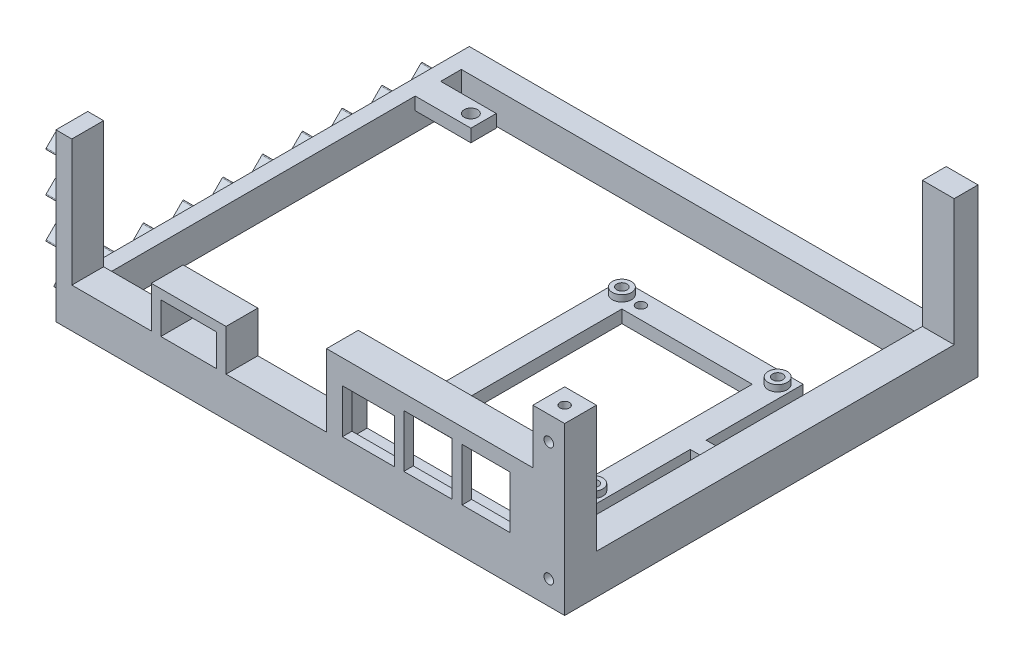
SolidWorks part; units mm, degrees
note: The reader was unsure of these and kept them because the rebuilt part matched: shared geometry of "Sketch14<3>".
ref_plane "Front Plane" through (0, 0, 0) normal (0, 0, 1) x (1, 0, 0)
ref_plane "Top Plane" through (0, 0, 0) normal (0, 1, 0) x (1, 0, 0)
ref_plane "Right Plane" through (0, 0, 0) normal (1, 0, 0) x (0, 0, -1)
sketch "Sketch1" plane through (0, 0, 0) normal (0, 1, 0) x (1, 0, 0)
  line L0 (0, -65) -> (0, 65) construction
  line L1 (-75, -65) -> (85, -65)
  line L2 (-75, -65) -> (-75, 65)
  line L3 (-75, 65) -> (85, 65)
  line L4 (85, -65) -> (85, 65)
  point P0 (0, 0)
  point P9 (0, 0)
  dimension "D1" = 75
  dimension "D2" = 85
extrude "Boss-Extrude1" add sketch "Sketch1" along normal blind 10
sketch "Sketch3" plane through (0, 10, 0) normal (0, 1, 0) x (1, 0, 0)
  line L6 (85, 65) -> (-75, 65) construction
  line L9 (-75, 65) -> (-75, -65) construction
  line L10 (75, 65) -> (75, -55)
  line L13 (75, -55) -> (-75, -55)
  line L14 (-75, -55) -> (-75, -65)
  line L15 (-75, -65) -> (85, -65)
  line L16 (85, -65) -> (85, 65)
  line L17 (85, 65) -> (75, 65)
  dimension "D1" = 10
extrude "Boss-Extrude2" add sketch "Sketch3" along normal blind 42.3
sketch "Sketch8" plane through (0, 0, -65) normal (0, 0, -1) x (-1, 0, 0)
  line L0 (-75, 10) -> (-85, 10) construction
  line L56 (-85, 52.3) -> (-85, 0) construction
  line L57 (-75, 10) -> (-75, 0) construction
  line L59 (-85, 0) -> (75, 0) construction
  line L60 (-80, 10) -> (-80, 52.3) construction
  line L126 (-85, 52.3) -> (-75, 52.3) construction
  line L139 (-75, 5) -> (75, 5) construction
  line L140 (75, 10) -> (75, 0) construction
  line L141 (-83.425, 31.15) -> (-76.575, 31.15) construction
  line L142 (-83.425, 31.15) -> (-80, 34.575)
  line L143 (-80, 34.575) -> (-76.575, 31.15)
  line L144 (-76.575, 31.15) -> (-80, 27.725)
  line L145 (-80, 27.725) -> (-83.425, 31.15)
  line L146 (-80, 40.225) -> (-83.425, 43.65)
  line L147 (-83.425, 43.65) -> (-80, 47.075)
  line L148 (-80, 47.075) -> (-76.575, 43.65)
  line L149 (-76.575, 43.65) -> (-80, 40.225)
  line L150 (-80, 15.225) -> (-83.425, 18.65)
  line L151 (-83.425, 18.65) -> (-80, 22.075)
  line L152 (-80, 22.075) -> (-76.575, 18.65)
  line L153 (-76.575, 18.65) -> (-80, 15.225)
  line L154 (0, 1.575) -> (0, 8.425) construction
  line L155 (0, 8.425) -> (-3.425, 5)
  line L156 (-3.425, 5) -> (0, 1.575)
  line L157 (0, 1.575) -> (3.425, 5)
  line L158 (3.425, 5) -> (0, 8.425)
  line L159 (15.925, 5) -> (12.5, 8.425)
  line L160 (12.5, 8.425) -> (9.075, 5)
  line L161 (9.075, 5) -> (12.5, 1.575)
  line L162 (12.5, 1.575) -> (15.925, 5)
  line L163 (28.425, 5) -> (25, 8.425)
  line L164 (25, 8.425) -> (21.575, 5)
  line L165 (21.575, 5) -> (25, 1.575)
  line L166 (25, 1.575) -> (28.425, 5)
  line L167 (40.925, 5) -> (37.5, 8.425)
  line L168 (37.5, 8.425) -> (34.075, 5)
  line L169 (34.075, 5) -> (37.5, 1.575)
  line L170 (37.5, 1.575) -> (40.925, 5)
  line L171 (53.425, 5) -> (50, 8.425)
  line L172 (50, 8.425) -> (46.575, 5)
  line L173 (46.575, 5) -> (50, 1.575)
  line L174 (50, 1.575) -> (53.425, 5)
  line L175 (65.925, 5) -> (62.5, 8.425)
  line L176 (62.5, 8.425) -> (59.075, 5)
  line L177 (59.075, 5) -> (62.5, 1.575)
  line L178 (62.5, 1.575) -> (65.925, 5)
  line L179 (-9.075, 5) -> (-12.5, 8.425)
  line L180 (-12.5, 8.425) -> (-15.925, 5)
  line L181 (-15.925, 5) -> (-12.5, 1.575)
  line L182 (-12.5, 1.575) -> (-9.075, 5)
  line L183 (-21.575, 5) -> (-25, 8.425)
  line L184 (-25, 8.425) -> (-28.425, 5)
  line L185 (-28.425, 5) -> (-25, 1.575)
  line L186 (-25, 1.575) -> (-21.575, 5)
  line L187 (-34.075, 5) -> (-37.5, 8.425)
  line L188 (-37.5, 8.425) -> (-40.925, 5)
  line L189 (-40.925, 5) -> (-37.5, 1.575)
  line L190 (-37.5, 1.575) -> (-34.075, 5)
  line L191 (-46.575, 5) -> (-50, 8.425)
  line L192 (-50, 8.425) -> (-53.425, 5)
  line L193 (-53.425, 5) -> (-50, 1.575)
  line L194 (-50, 1.575) -> (-46.575, 5)
  line L195 (-59.075, 5) -> (-62.5, 8.425)
  line L196 (-62.5, 8.425) -> (-65.925, 5)
  line L197 (-65.925, 5) -> (-62.5, 1.575)
  line L198 (-62.5, 1.575) -> (-59.075, 5)
  line L199 (-71.575, 5) -> (-75, 8.425)
  line L200 (-75, 8.425) -> (-78.425, 5)
  line L201 (-78.425, 5) -> (-75, 1.575)
  line L202 (-75, 1.575) -> (-71.575, 5)
  point P18 (-80, 31.15)
  point P31 (0, 5)
  dimension "D1" = 2
  dimension "D2" = 2
extrude "Cut-Extrude3" cut sketch "Sketch8" against normal blind 5.25
sketch "Sketch9" plane through (0, 10, 0) normal (0, 1, 0) x (1, 0, 0)
  line L1 (-75, 65) -> (-75, -55) construction
  line L5 (-70, -55) -> (75, -55)
  line L6 (-70, 51) -> (-70, 57.5)
  line L7 (-70, 43) -> (-70, -55)
  line L8 (75, -55) -> (75, 57.5)
  line L9 (75, 65) -> (75, -55) construction
  line L10 (75, 57.5) -> (-70, 57.5)
  line L12 (75, 65) -> (-75, 65) construction
  line L13 (-52.5, 47) -> (-56.5, 47) construction
  line L14 (-70, 43) -> (-52.5, 43)
  line L15 (-52.5, 43) -> (-52.5, 51)
  line L16 (-52.5, 51) -> (-70, 51)
  circle A1 centre (-56.5, 47) radius 2.1
  dimension "D2" = 4.2
  dimension "D4" = 5
  dimension "D1" = 7.5
  dimension "D5" = 17.5
extrude "Cut-Extrude4" cut sketch "Sketch9" against normal through all
sketch "Sketch10" plane through (-75, 0, 0) normal (-1, 0, 0) x (0, 0, 1)
  line L0 (55, 10) -> (65, 10) construction
  line L1 (10.5379, 5.2121) -> (7.7121, 8.0379)
  line L2 (7.2879, 8.0379) -> (4.4621, 5.2121)
  line L40 (65, 52.3) -> (65, 0) construction
  line L41 (55, 10) -> (55, 0) construction
  line L42 (-65, 0) -> (65, 0) construction
  line L43 (4.4621, 4.7879) -> (7.2879, 1.9621)
  line L57 (60, 10) -> (60, 52.3) construction
  line L94 (55, 52.3) -> (65, 52.3) construction
  line L111 (63.25, 31.15) -> (56.75, 31.15) construction
  line L112 (56.9621, 31.3621) -> (59.7879, 34.1879)
  line L113 (60.2121, 34.1879) -> (63.0379, 31.3621)
  line L114 (63.0379, 30.9379) -> (60.2121, 28.1121)
  line L115 (59.7879, 28.1121) -> (56.9621, 30.9379)
  line L124 (55, 5) -> (-65, 5) construction
  line L125 (-65, 10) -> (-65, 0) construction
  line L126 (-5, 8.25) -> (-5, 1.75) construction
  line L127 (-5.2121, 8.0379) -> (-8.0379, 5.2121)
  line L128 (-8.0379, 4.7879) -> (-5.2121, 1.9621)
  line L129 (-4.7879, 1.9621) -> (-1.9621, 4.7879)
  line L130 (-1.9621, 5.2121) -> (-4.7879, 8.0379)
  line L131 (59.7879, 40.6121) -> (56.9621, 43.4379)
  line L132 (56.9621, 43.8621) -> (59.7879, 46.6879)
  line L133 (60.2121, 46.6879) -> (63.0379, 43.8621)
  line L134 (63.0379, 43.4379) -> (60.2121, 40.6121)
  line L135 (59.7879, 15.6121) -> (56.9621, 18.4379)
  line L136 (56.9621, 18.8621) -> (59.7879, 21.6879)
  line L137 (60.2121, 21.6879) -> (63.0379, 18.8621)
  line L138 (63.0379, 18.4379) -> (60.2121, 15.6121)
  line L139 (7.7121, 1.9621) -> (10.5379, 4.7879)
  line L140 (23.0379, 5.2121) -> (20.2121, 8.0379)
  line L141 (19.7879, 8.0379) -> (16.9621, 5.2121)
  line L142 (16.9621, 4.7879) -> (19.7879, 1.9621)
  line L143 (20.2121, 1.9621) -> (23.0379, 4.7879)
  line L144 (35.5379, 5.2121) -> (32.7121, 8.0379)
  line L145 (32.2879, 8.0379) -> (29.4621, 5.2121)
  line L146 (29.4621, 4.7879) -> (32.2879, 1.9621)
  line L147 (32.7121, 1.9621) -> (35.5379, 4.7879)
  line L148 (48.0379, 5.2121) -> (45.2121, 8.0379)
  line L149 (44.7879, 8.0379) -> (41.9621, 5.2121)
  line L150 (41.9621, 4.7879) -> (44.7879, 1.9621)
  line L151 (45.2121, 1.9621) -> (48.0379, 4.7879)
  line L152 (60.5379, 5.2121) -> (57.7121, 8.0379)
  line L153 (57.2879, 8.0379) -> (54.4621, 5.2121)
  line L154 (54.4621, 4.7879) -> (57.2879, 1.9621)
  line L155 (57.7121, 1.9621) -> (60.5379, 4.7879)
  line L156 (-14.4621, 5.2121) -> (-17.2879, 8.0379)
  line L157 (-17.7121, 8.0379) -> (-20.5379, 5.2121)
  line L158 (-20.5379, 4.7879) -> (-17.7121, 1.9621)
  line L159 (-17.2879, 1.9621) -> (-14.4621, 4.7879)
  line L160 (-26.9621, 5.2121) -> (-29.7879, 8.0379)
  line L161 (-30.2121, 8.0379) -> (-33.0379, 5.2121)
  line L162 (-33.0379, 4.7879) -> (-30.2121, 1.9621)
  line L163 (-29.7879, 1.9621) -> (-26.9621, 4.7879)
  line L164 (-39.4621, 5.2121) -> (-42.2879, 8.0379)
  line L165 (-42.7121, 8.0379) -> (-45.5379, 5.2121)
  line L166 (-45.5379, 4.7879) -> (-42.7121, 1.9621)
  line L167 (-42.2879, 1.9621) -> (-39.4621, 4.7879)
  line L168 (-51.9621, 5.2121) -> (-54.7879, 8.0379)
  line L169 (-55.2121, 8.0379) -> (-58.0379, 5.2121)
  line L170 (-58.0379, 4.7879) -> (-55.2121, 1.9621)
  line L171 (-54.7879, 1.9621) -> (-51.9621, 4.7879)
  arc A100 (-4.7879, 1.9621) -> (-5.2121, 1.9621) centre (-5, 2.1743) cw
  arc A101 (-8.0379, 5.2121) -> (-8.0379, 4.7879) centre (-7.8257, 5) ccw
  arc A102 (-1.9621, 4.7879) -> (-1.9621, 5.2121) centre (-2.1743, 5) ccw
  arc A103 (-4.7879, 8.0379) -> (-5.2121, 8.0379) centre (-5, 7.8257) ccw
  arc A104 (56.9621, 30.9379) -> (56.9621, 31.3621) centre (57.1743, 31.15) cw
  arc A105 (60.2121, 28.1121) -> (59.7879, 28.1121) centre (60, 28.3243) cw
  arc A106 (63.0379, 30.9379) -> (63.0379, 31.3621) centre (62.8257, 31.15) ccw
  arc A107 (59.7879, 34.1879) -> (60.2121, 34.1879) centre (60, 33.9757) cw
  arc A108 (60.2121, 40.6121) -> (59.7879, 40.6121) centre (60, 40.8243) cw
  arc A109 (56.9621, 43.4379) -> (56.9621, 43.8621) centre (57.1743, 43.65) cw
  arc A110 (59.7879, 46.6879) -> (60.2121, 46.6879) centre (60, 46.4757) cw
  arc A111 (63.0379, 43.4379) -> (63.0379, 43.8621) centre (62.8257, 43.65) ccw
  arc A112 (60.2121, 15.6121) -> (59.7879, 15.6121) centre (60, 15.8243) cw
  arc A113 (56.9621, 18.4379) -> (56.9621, 18.8621) centre (57.1743, 18.65) cw
  arc A114 (59.7879, 21.6879) -> (60.2121, 21.6879) centre (60, 21.4757) cw
  arc A115 (63.0379, 18.4379) -> (63.0379, 18.8621) centre (62.8257, 18.65) ccw
  arc A116 (7.7121, 8.0379) -> (7.2879, 8.0379) centre (7.5, 7.8257) ccw
  arc A117 (10.5379, 4.7879) -> (10.5379, 5.2121) centre (10.3257, 5) ccw
  arc A118 (4.4621, 5.2121) -> (4.4621, 4.7879) centre (4.6743, 5) ccw
  arc A119 (7.7121, 1.9621) -> (7.2879, 1.9621) centre (7.5, 2.1743) cw
  arc A120 (20.2121, 8.0379) -> (19.7879, 8.0379) centre (20, 7.8257) ccw
  arc A121 (23.0379, 4.7879) -> (23.0379, 5.2121) centre (22.8257, 5) ccw
  arc A122 (16.9621, 5.2121) -> (16.9621, 4.7879) centre (17.1743, 5) ccw
  arc A123 (20.2121, 1.9621) -> (19.7879, 1.9621) centre (20, 2.1743) cw
  arc A124 (32.7121, 8.0379) -> (32.2879, 8.0379) centre (32.5, 7.8257) ccw
  arc A125 (35.5379, 4.7879) -> (35.5379, 5.2121) centre (35.3257, 5) ccw
  arc A126 (29.4621, 5.2121) -> (29.4621, 4.7879) centre (29.6743, 5) ccw
  arc A127 (32.7121, 1.9621) -> (32.2879, 1.9621) centre (32.5, 2.1743) cw
  arc A128 (45.2121, 8.0379) -> (44.7879, 8.0379) centre (45, 7.8257) ccw
  arc A129 (48.0379, 4.7879) -> (48.0379, 5.2121) centre (47.8257, 5) ccw
  arc A130 (41.9621, 5.2121) -> (41.9621, 4.7879) centre (42.1743, 5) ccw
  arc A131 (45.2121, 1.9621) -> (44.7879, 1.9621) centre (45, 2.1743) cw
  arc A132 (57.7121, 8.0379) -> (57.2879, 8.0379) centre (57.5, 7.8257) ccw
  arc A133 (60.5379, 4.7879) -> (60.5379, 5.2121) centre (60.3257, 5) ccw
  arc A134 (54.4621, 5.2121) -> (54.4621, 4.7879) centre (54.6743, 5) ccw
  arc A135 (57.7121, 1.9621) -> (57.2879, 1.9621) centre (57.5, 2.1743) cw
  arc A136 (-17.2879, 8.0379) -> (-17.7121, 8.0379) centre (-17.5, 7.8257) ccw
  arc A137 (-14.4621, 4.7879) -> (-14.4621, 5.2121) centre (-14.6743, 5) ccw
  arc A138 (-20.5379, 5.2121) -> (-20.5379, 4.7879) centre (-20.3257, 5) ccw
  arc A139 (-17.2879, 1.9621) -> (-17.7121, 1.9621) centre (-17.5, 2.1743) cw
  arc A140 (-29.7879, 8.0379) -> (-30.2121, 8.0379) centre (-30, 7.8257) ccw
  arc A141 (-26.9621, 4.7879) -> (-26.9621, 5.2121) centre (-27.1743, 5) ccw
  arc A142 (-33.0379, 5.2121) -> (-33.0379, 4.7879) centre (-32.8257, 5) ccw
  arc A143 (-29.7879, 1.9621) -> (-30.2121, 1.9621) centre (-30, 2.1743) cw
  arc A144 (-42.2879, 8.0379) -> (-42.7121, 8.0379) centre (-42.5, 7.8257) ccw
  arc A145 (-39.4621, 4.7879) -> (-39.4621, 5.2121) centre (-39.6743, 5) ccw
  arc A146 (-45.5379, 5.2121) -> (-45.5379, 4.7879) centre (-45.3257, 5) ccw
  arc A147 (-42.2879, 1.9621) -> (-42.7121, 1.9621) centre (-42.5, 2.1743) cw
  arc A148 (-54.7879, 8.0379) -> (-55.2121, 8.0379) centre (-55, 7.8257) ccw
  arc A149 (-51.9621, 4.7879) -> (-51.9621, 5.2121) centre (-52.1743, 5) ccw
  arc A150 (-58.0379, 5.2121) -> (-58.0379, 4.7879) centre (-57.8257, 5) ccw
  arc A151 (-54.7879, 1.9621) -> (-55.2121, 1.9621) centre (-55, 2.1743) cw
  point P14 (60, 31.15)
  point P23 (-8.25, 5)
  point P31 (-5, 5)
  point P32 (-1.75, 5)
  point P42 (60, 27.9)
  point P48 (60, 34.4)
  dimension "D1" = 0.3
  dimension "D3" = 2
  dimension "D2" = 2
sketch "Sketch11" plane through (75, 0, 0) normal (-1, 0, 0) x (0, 0, 1)
  line L1 (-65, 52.3) -> (55, 52.3) construction
  line L2 (-57.5, 52.3) -> (55, 52.3)
  line L6 (-57.5, 52.3) -> (-57.5, 12.5)
  line L7 (-57.5, 12.5) -> (55, 12.5)
  line L8 (55, 52.3) -> (55, 0) construction
  line L9 (55, 12.5) -> (55, 52.3)
  line L10 (55, 0) -> (-57.5, 0) construction
  dimension "D1" = 12.5
extrude "Cut-Extrude5" cut sketch "Sketch11" against normal through all
sketch "Sketch14" plane through (0, 0, 0) normal (0, 1, 0) x (1, 0, 0)
  line L0 (65.5, -36.5) -> (75, -36.5) construction
  line L1 (49.5, -7.5) -> (75.0071, -7.5) construction
  line L2 (65.5, -36.5) -> (65.5, -55) construction
  line L3 (75, -55) -> (75, 57.5) construction
  line L4 (75, 57.5) -> (75, -55) construction
  line L5 (65.5, -36.5) -> (16.5, -36.5) construction
  line L6 (16.5, -36.5) -> (16.5, 21.5) construction
  line L7 (16.5, 21.5) -> (65.5, 21.5) construction
  line L8 (65.5, 21.5) -> (65.5, -36.5) construction
  line L9 (41, -36.5) -> (41, 21.5) construction
  line L10 (16.5, -7.5) -> (65.5, -7.5) construction
  line L11 (58.5002, -55) -> (23.4998, -55)
  line L12 (61.5, 17.5) -> (20.5, 17.5)
  line L13 (61.5, 17.5) -> (61.5, -32.5)
  line L14 (61.5, -32.5) -> (20.5, -32.5)
  line L15 (20.5, 17.5) -> (20.5, -32.5)
  line L16 (69.5, 25.5) -> (12.5, 25.5)
  line L17 (69.5, 25.5) -> (69.5, -5)
  line L18 (69.5, -40.5) -> (23.4998, -40.5)
  line L19 (12.5, 25.5) -> (12.5, -40.5)
  line L20 (58.5002, -55) -> (58.5002, -40.5)
  line L22 (58.5002, -40.5) -> (12.5, -40.5)
  line L23 (75.0142, -5) -> (75, -10)
  line L24 (75.0142, -5) -> (69.5, -5)
  line L25 (75, -10) -> (69.5, -10)
  line L26 (69.5, -10) -> (69.5, -40.5)
  line L27 (41, -36.5) -> (41, -55) construction
  line L28 (-70, -55) -> (75, -55) construction
  line L29 (23.4998, -40.5) -> (23.4998, -55)
  circle A0 centre (65.5, -36.5) radius 1.625
  circle A1 centre (16.5, -36.5) radius 1.625
  circle A2 centre (16.5, 21.5) radius 1.625
  circle A3 centre (65.5, 21.5) radius 1.625
  circle A4 centre (22.5, 21.5) radius 1.5
  circle A5 centre (59.5, -36.5) radius 1.5
  circle A6 centre (16.5, -36.5) radius 3
  circle A7 centre (65.5, -36.5) radius 3
  circle A8 centre (16.5, 21.5) radius 3
  circle A9 centre (65.5, 21.5) radius 3
  point P26 (41, -7.5)
  point P31 (41, -7.5)
  point P41 (41, -55)
  point P46 (75.0071, -7.5)
  dimension "D1" = 6
  dimension "D3" = 4
  dimension "D14" = 3.25
  dimension "D15" = 3.25
  dimension "D16" = 3.25
  dimension "D17" = 3.25
  dimension "D2" = 6
  dimension "D4" = 4
  dimension "D5" = 4
  dimension "D6" = 4
  dimension "D7" = 58
  dimension "D8" = 49
  dimension "D9" = 4
  dimension "D10" = 4
  dimension "D11" = 4
  dimension "D12" = 4
  dimension "D13" = 5.5
extrude "Boss-Extrude7" add sketch "Sketch14" along normal blind 10 contours L26 L25 L23 L24 L17 L16 L19 L22 L20 L11 L29 L18 A9 A8 A7 A6 A5 A4 L15 L12 L13 L14 | A7 A0 | A6 A1 | A8 A2 | A9 A3
extrude "Boss-Extrude8" add sketch "Sketch14<3>" along normal blind 12 contours A8 A2 | A9 A3 | A7 A0 | A6 A1
sketch "Sketch14<3>" plane through (0, 0, 0) normal (0, 1, 0) x (1, 0, 0) same geometry as "Sketch14"
sketch "Sketch15" plane through (0, 52.3, 0) normal (0, 1, 0) x (1, 0, 0)
  line L0 (80, -60) -> (85, -60) construction
  line L2 (85, -65) -> (85, -55) construction
  line L3 (80, -60) -> (80, -65) construction
  line L4 (-75, -65) -> (85, -65) construction
  circle A0 centre (80, -60) radius 1.5
extrude "Cut-Extrude7" cut sketch "Sketch15" against normal blind 4
sketch "Sketch16" plane through (0, 0, 0) normal (0, -1, 0) x (1, 0, 0)
  circle A0 centre (80, 60) radius 1.5 construction
  circle A1 centre (80, 60) radius 1.5
extrude "Cut-Extrude8" cut sketch "Sketch16" against normal blind 4
sketch "Sketch17" plane through (0, 0, 0) normal (0, -1, 0) x (1, 0, 0)
  line L4 (-70, -43) -> (-70, -51)
  line L5 (-70, -51) -> (-52.5, -51)
  line L6 (-52.5, -51) -> (-52.5, -43)
  line L7 (-52.5, -43) -> (-70, -43)
extrude "Cut-Extrude9" cut sketch "Sketch17" against normal blind 6
sketch "Sketch18" plane through (0, 0, 0) normal (0, -1, 0) x (1, 0, 0)
  line L0 (12.5, -25.5) -> (12.5, 55)
  line L1 (-70, 55) -> (75, 55) construction
  line L2 (12.5, 55) -> (75, 55)
  line L3 (12.5, -25.5) -> (75, -25.5)
  line L5 (75, 5) -> (75, -57.5) construction
  line L6 (75, -25.5) -> (75, 55)
extrude "Cut-Extrude10" cut sketch "Sketch18" against normal blind 6
sketch "Sketch19" plane through (0, 0, 65) normal (0, 0, 1) x (1, 0, 0)
  line L0 (80, 7.5) -> (85, 7.5) construction
  line L1 (85, 52.3) -> (85, 0) construction
  line L2 (80, 7.5) -> (80, 0) construction
  line L4 (80, 44.8) -> (85, 44.8) construction
  line L6 (80, 44.8) -> (80, 52.3) construction
  line L7 (-75, 0) -> (85, 0) construction
  line L9 (-75, 52.3) -> (85, 52.3) construction
  circle A0 centre (80, 7.5) radius 1.5
  circle A1 centre (80, 44.8) radius 1.5
extrude "Cut-Extrude11" cut sketch "Sketch19" against normal blind 4
sketch "Sketch21" plane through (0, 0, 65) normal (0, 0, 1) x (1, 0, 0)
  line L4 (-75, 52.3) -> (-75, 0) construction
  line L19 (-70, 12.5) -> (-70, 52.3)
  line L20 (-70, 52.3) -> (75, 52.3)
  line L24 (-75, 0) -> (85, 0) construction
  line L26 (-45, 12.5) -> (-70, 12.5)
  line L28 (85, 52.3) -> (85, 0) construction
  line L29 (85, 12.5) -> (85, 52.3)
  line L38 (-33.25, 25.5) -> (-33.25, 12.5) construction
  line L40 (15.1, 27.65) -> (15.1, 13.75)
  line L41 (-45, 25.5) -> (-45, 12.5)
  line L44 (15.1, 13.75) -> (31.5, 13.75)
  line L45 (31.5, 13.75) -> (31.5, 27.65)
  line L46 (31.5, 27.65) -> (15.1, 27.65)
  line L47 (34.4, 13.9581) -> (34.4, 30.5419)
  line L48 (34.4, 30.5419) -> (49.6, 30.5419)
  line L49 (49.6, 30.5419) -> (49.6, 13.9581)
  line L50 (49.6, 13.9581) -> (34.4, 13.9581)
  line L54 (52.75, 13.9991) -> (52.75, 30.5009)
  line L55 (12.9, 32.25) -> (69.9, 32.25)
  line L57 (69.9, 32.25) -> (69.9, 10)
  line L58 (69.9, 12.5) -> (75, 12.5)
  line L59 (69.9, 10) -> (12.9, 10)
  line L60 (12.9, 10) -> (12.9, 32.25)
  line L61 (29, 35.25) -> (29, 12.5) construction
  line L62 (10.1, 25.5) -> (10.1, 35.25)
  line L63 (29, 35.25) -> (75, 35.25)
  line L64 (10.1, 35.25) -> (29, 35.25)
  line L65 (75, 52.3) -> (75, 0)
  line L66 (75, 0) -> (-70, 0)
  line L67 (-70, 0) -> (-70, 12.5)
  line L68 (-70, 12.5) -> (-70, 0)
  line L70 (67.75, 30.5009) -> (67.75, 13.9991)
  line L72 (52.75, 30.5009) -> (67.75, 30.5009)
  line L73 (67.75, 13.9991) -> (52.75, 13.9991)
  line L74 (15.1, 27.65) -> (31.5, 13.75) construction
  line L75 (15.1, 13.75) -> (31.5, 27.65) construction
  line L76 (34.4, 30.5419) -> (49.6, 13.9581) construction
  line L77 (34.4, 13.9581) -> (49.6, 30.5419) construction
  line L78 (52.75, 30.5009) -> (67.75, 13.9991) construction
  line L79 (52.75, 13.9991) -> (67.75, 30.5009) construction
  line L80 (23.3, 20.7) -> (23.3, 35.25) construction
  line L81 (42, 22.25) -> (42, 35.25) construction
  line L82 (60.25, 22.25) -> (60.25, 35.25) construction
  line L83 (10.1, 25.5) -> (10.1, 12.5)
  line L84 (10.1, 12.5) -> (69.9, 12.5) construction
  line L85 (-21.5, 12.5) -> (-21.5, 25.5)
  line L86 (10.1, 12.5) -> (-21.5, 12.5)
  line L87 (-42, 22.5) -> (-42, 12.5)
  line L88 (-42, 12.5) -> (-24.5, 12.5)
  line L89 (-24.5, 22.5) -> (-24.5, 12.5)
  line L90 (-42, 22.5) -> (-24.5, 22.5)
  line L91 (-45, 25.5) -> (-21.5, 25.5)
  dimension "D2" = 10
  dimension "D3" = 2.8
  dimension "D4" = 3
  dimension "D5" = 10
  dimension "D1" = 5
  dimension "D6" = 12.5
  dimension "D7" = 3
  dimension "D8" = 12.5
  dimension "D9" = 12.5
  dimension "D10" = 17.5
  dimension "D11" = 13.9
  dimension "D12" = 16.5838
  dimension "D13" = 16.5018
  dimension "D14" = 16.4
  dimension "D15" = 15.2
  dimension "D16" = 15
  dimension "D17" = 43.35
  dimension "D18" = 3
extrude "Cut-Extrude14" cut sketch "Sketch21" against normal blind 10
sketch "Sketch22" plane through (0, 0, 55) normal (0, 0, -1) x (-1, 0, 0)
  line L0 (-69.9, 32.25) -> (-69.9, 10) construction
  line L1 (-69.9, 10) -> (-12.9, 10) construction
  line L2 (-12.9, 10) -> (-12.9, 32.25) construction
  line L3 (-12.9, 32.25) -> (-69.9, 32.25) construction
  line L4 (-69.9, 32.25) -> (-69.9, 10)
  line L5 (-69.9, 10) -> (-12.9, 10)
  line L6 (-12.9, 10) -> (-12.9, 32.25)
  line L7 (-12.9, 32.25) -> (-69.9, 32.25)
extrude "Cut-Extrude16" cut sketch "Sketch22" against normal blind 7
extrude "Boss-Extrude9" add sketch "Sketch10" along normal blind 5
